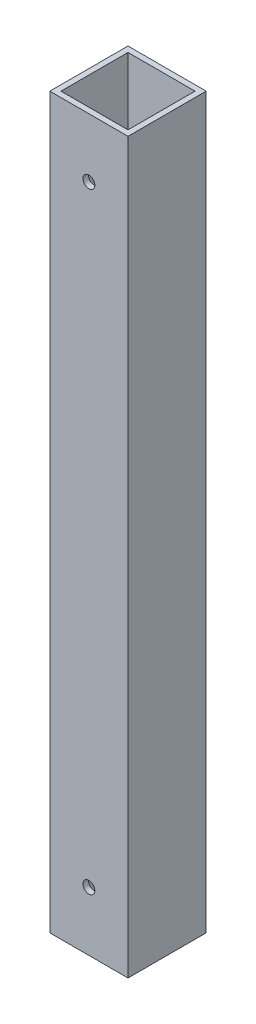
SolidWorks part; units mm, degrees
material "6061-T6 (SS)"
ref_plane "Front Plane" through (0, 0, 0) normal (0, 0, 1) x (1, 0, 0)
ref_plane "Top Plane" through (0, 0, 0) normal (0, 1, 0) x (1, 0, 0)
ref_plane "Right Plane" through (0, 0, 0) normal (1, 0, 0) x (0, 0, -1)
sketch "Sketch1" plane through (0, 0, 0) normal (0, 1, 0) x (1, 0, 0)
  line L1 (-22.225, -22.225) -> (22.225, -22.225)
  line L2 (-22.225, -22.225) -> (-22.225, 22.225)
  line L3 (-22.225, 22.225) -> (22.225, 22.225)
  line L4 (22.225, -22.225) -> (22.225, 22.225)
  line L5 (-22.225, -22.225) -> (22.225, 22.225) construction
  line L6 (-22.225, 22.225) -> (22.225, -22.225) construction
  line L7 (-19.05, -19.05) -> (19.05, -19.05)
  line L8 (-19.05, -19.05) -> (-19.05, 19.05)
  line L9 (-19.05, 19.05) -> (19.05, 19.05)
  line L10 (19.05, -19.05) -> (19.05, 19.05)
  line L11 (-19.05, -19.05) -> (19.05, 19.05) construction
  line L12 (-19.05, 19.05) -> (19.05, -19.05) construction
  point P0 (0, 0)
  point P6 (0, 0)
  point P11 (0, 22.225)
  dimension "D1" = 44.45
  dimension "D2" = 3.175
extrude "Boss-Extrude1" add sketch "Sketch1" along normal blind 207.1687 and the other way blind 207.1687
hole_wizard "17/64 (0.26563) Diameter Hole1" positions "Sketch2" profile "Sketch3" hole size "17/64" standard "ANSI Inch" end condition through all
sketch "Sketch2" plane through (0, 0, 22.225) normal (0, 0, 1) x (1, 0, 0)
  line L0 (0, -173.609) -> (0, 173.609) construction
  point P0 (0, 173.609)
  point P2 (0, -173.609)
  dimension "D1" = 173.609
sketch "Sketch3" plane through (0, 173.609, 22.225) normal (1, 0, 0) x (0, -1, 0)
  line L0 (0, 0) -> (0, 44.45)
  line L1 (0, 44.45) -> (3.3735, 44.45)
  line L2 (3.3735, 44.45) -> (3.3735, 0)
  line L5 (3.3735, 0) -> (0, 0)
  line L11 (0, -6.35) -> (0, 107.95) construction
  dimension "Thru Hole Dia." = 6.747
  dimension "Thru Hole Depth" = 44.45
